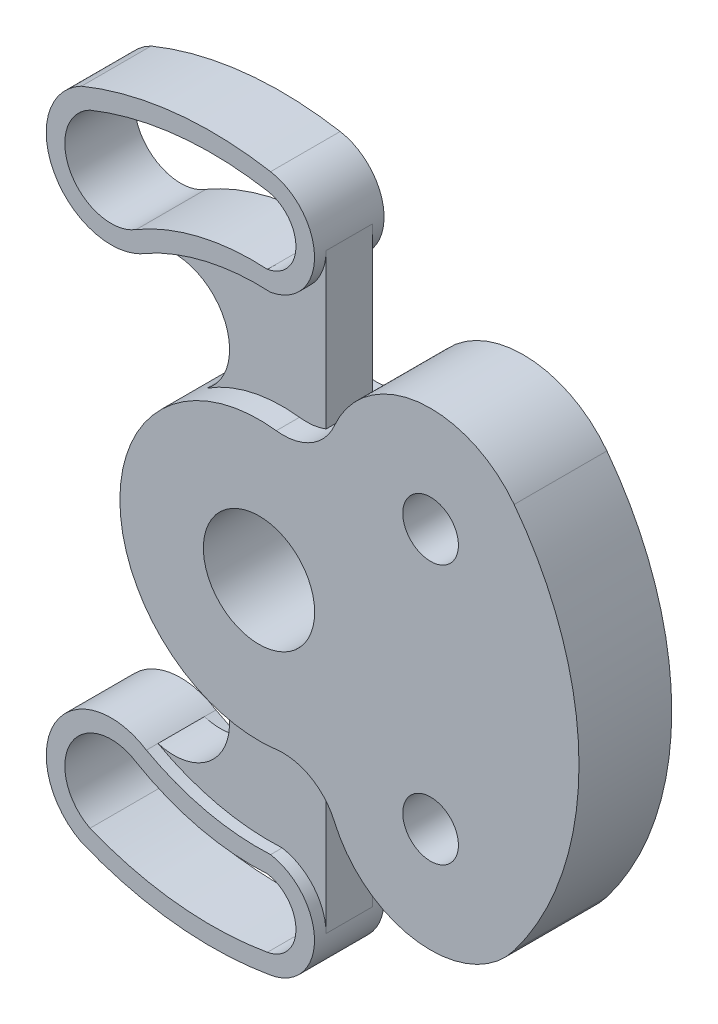
SolidWorks part; units mm, degrees
ref_plane "Front Plane" through (0, 0, 0) normal (0, 0, 1) x (1, 0, 0)
ref_plane "Top Plane" through (0, 0, 0) normal (0, 1, 0) x (1, 0, 0)
ref_plane "Right Plane" through (0, 0, 0) normal (1, 0, 0) x (0, 0, -1)
sketch "Sketch1" plane through (0, 0, 0) normal (0, 0, 1) x (1, 0, 0)
  line L0 (0, 60.6405) -> (0, -66.8868) construction
  line L1 (-99.3152, 0) -> (136.5844, 0) construction
  circle A0 centre (0, 0) radius 30
  circle A1 centre (0, 0) radius 12
  circle A2 centre (37, 28) radius 6
  circle A3 centre (37, -28) radius 6
  arc A4 (55.021, 41.6375) -> (16.2404, 36.932) centre (37, 28) ccw
  arc A5 (16.2404, -36.932) -> (55.021, -41.6375) centre (37, -28) ccw
  arc A8 (55.021, -41.6375) -> (55.021, 41.6375) centre (0, 0) ccw
  arc A9 (3.7267, 29.7676) -> (16.2404, 36.932) centre (5.2174, 41.6747) ccw
  arc A10 (16.2404, -36.932) -> (3.7267, -29.7676) centre (5.2174, -41.6747) ccw
  dimension "D1" = 60
  dimension "D2" = 37
  dimension "D3" = 37
  dimension "D4" = 28
  dimension "D5" = 28
  dimension "D6" = 138
extrude "Boss-Extrude1" add sketch "Sketch1" against normal blind 20 contours A10 A5 A8 A4 A9 A0 A3 A2 | A0 A1 region at (21.8561, -19.2904, 0) region at (42.204, 0, 0)
ref_plane "Plane1" through (0, 0, -10) normal (0, 0, 1) x (1, 0, 0)
sketch "Sketch2" plane through (0, 0, -10) normal (0, 0, 1) x (1, 0, 0)
  line L0 (0, 84.166) -> (0, -85.2837) construction
  line L1 (11.1796, 31.2607) -> (11.1796, 67.1763)
  line L2 (0, 0) -> (-50.3283, 87.1711) construction
  line L3 (-40.768, 70.6122) -> (-26.7852, 46.3933)
  line L4 (0, 75.0293) -> (0, 52.507)
  line L5 (-75.8534, 0) -> (116.6227, 0) construction
  line L6 (0, -75.0293) -> (0, -52.507)
  line L7 (-40.768, -70.6122) -> (-26.7852, -46.3933)
  arc A0 (3.7267, 29.7676) -> (16.2404, 36.932) centre (5.2174, 41.6747) ccw construction
  arc A1 (-26.7852, 46.3933) -> (-40.768, 70.6122) centre (-34.3774, 58.1559) cw
  arc A2 (0, 75.0293) -> (0, 52.507) centre (-1.9658, 63.7682) cw
  arc A3 (-40.768, 70.6122) -> (0, 75.0293) centre (-12.725, 2.1316) cw
  arc A4 (-26.7852, 46.3933) -> (0, 52.507) centre (-2.6944, 2.5797) cw
  arc A5 (-28.9544, 49.7541) -> (-38.9421, 67.0533) centre (-34.3774, 58.1559) cw
  arc A6 (-0.6878, 71.0889) -> (-0.6878, 56.4474) centre (-1.9658, 63.7682) cw
  arc A7 (-38.9421, 67.0533) -> (-0.6878, 71.0889) centre (-12.7537, 2.1367) cw
  arc A8 (-28.9544, 49.7541) -> (-0.6878, 56.4474) centre (-3.7968, 6.5442) cw
  arc A9 (-0.6878, -71.0889) -> (-0.6878, -56.4474) centre (-1.9658, -63.7682) ccw
  arc A10 (0, -75.0293) -> (0, -52.507) centre (-1.9658, -63.7682) ccw
  arc A11 (-26.7852, -46.3933) -> (0, -52.507) centre (-2.6944, -2.5797) ccw
  arc A12 (-28.9544, -49.7541) -> (-0.6878, -56.4474) centre (-3.7968, -6.5442) ccw
  arc A13 (-40.768, -70.6122) -> (0, -75.0293) centre (-12.725, -2.1316) ccw
  arc A14 (-38.9421, -67.0533) -> (-0.6878, -71.0889) centre (-12.7537, -2.1367) ccw
  arc A15 (-28.9544, -49.7541) -> (-38.9421, -67.0533) centre (-34.3774, -58.1559) ccw
  arc A16 (-26.7852, -46.3933) -> (-40.768, -70.6122) centre (-34.3774, -58.1559) ccw
  arc A17 (-29.3422, 45.0927) -> (-18.0772, 23.9419) centre (-24.2923, 34.2071) cw
  arc A19 (3.7267, 29.7676) -> (3.7267, -29.7676) centre (0, 0) ccw construction
  dimension "D2" = 14
  dimension "D3" = 50
  dimension "D4" = 74
  dimension "D5" = 4
  dimension "D1" = 30
extrude "Boss-Extrude2" add sketch "Sketch2" along normal mid plane 15 separate body contours L3 A7 A6 L4 A3 | A8 A5 A7 L3 A1 | L4 A6 A2 | A8 L3 A4 L4 A6 | A14 L7 A13 L6 A9 | L7 A16 A14 A15 A12 | L7 A12 A9 L6 A11 | L6 A10 A9 region at (-20.0662, 72.8261, -10) region at (-40.0579, 68.6993, -10) region at (9.2214, 63.7682, -10) region at (-14.2634, 52.6548, -10) region at (-20.0662, -72.8261, -10) region at (0.2443, -72.9821, -10) region at (-14.2634, -52.6548, -10) region at (-46.206, -51.3266, -10)
sketch "Sketch3" plane through (0, 0, -10) normal (0, 0, 1) x (1, 0, 0)
  line L0 (9.4657, 63.7682) -> (9.4657, 30.4518)
  line L1 (0, 0) -> (-51.476, 89.1591) construction
  line L2 (0, 0) -> (0, 107.4788) construction
  line L3 (-111.7886, 0) -> (106.8833, 0) construction
  line L4 (9.4657, -63.7682) -> (9.4657, -30.4518)
  arc A0 (0, 52.507) -> (0, 75.0293) centre (-1.9658, 63.7682) ccw construction
  arc A1 (3.7267, 29.7676) -> (16.2404, 36.932) centre (5.2174, 41.6747) ccw construction
  arc A2 (-26.7852, 46.3933) -> (-17.0712, 24.6693) centre (-23.3501, 34.8955) cw
  arc A7 (3.7267, 29.7676) -> (3.7267, -29.7676) centre (0, 0) ccw construction
  arc A8 (-26.7852, 46.3933) -> (0, 52.507) centre (-2.6944, 2.5797) cw
  arc A9 (-17.0712, 24.6693) -> (3.7267, 29.7676) centre (0, 0) cw
  arc A10 (0, 52.507) -> (9.4657, 63.7682) centre (-1.9658, 63.7682) ccw
  arc A11 (3.7267, 29.7676) -> (9.4657, 30.4518) centre (5.2174, 41.6747) ccw
  arc A12 (0, -52.507) -> (9.4657, -63.7682) centre (-1.9658, -63.7682) cw
  arc A13 (-26.7852, -46.3933) -> (0, -52.507) centre (-2.6944, -2.5797) ccw
  arc A14 (3.7267, -29.7676) -> (9.4657, -30.4518) centre (5.2174, -41.6747) cw
  arc A15 (-17.0712, -24.6693) -> (3.7267, -29.7676) centre (0, 0) ccw
  arc A16 (-26.7852, -46.3933) -> (-17.0712, -24.6693) centre (-23.3501, -34.8955) ccw
  dimension "D1" = 12
  dimension "D2" = 30
extrude "Boss-Extrude3" add sketch "Sketch3" along normal mid plane 10 contours A9 A11 L0 A10 A8 A2 | A16 A13 A12 L4 A14 A15 region at (-2.63, 42.1914, -10) region at (-2.63, -42.1914, -10)
